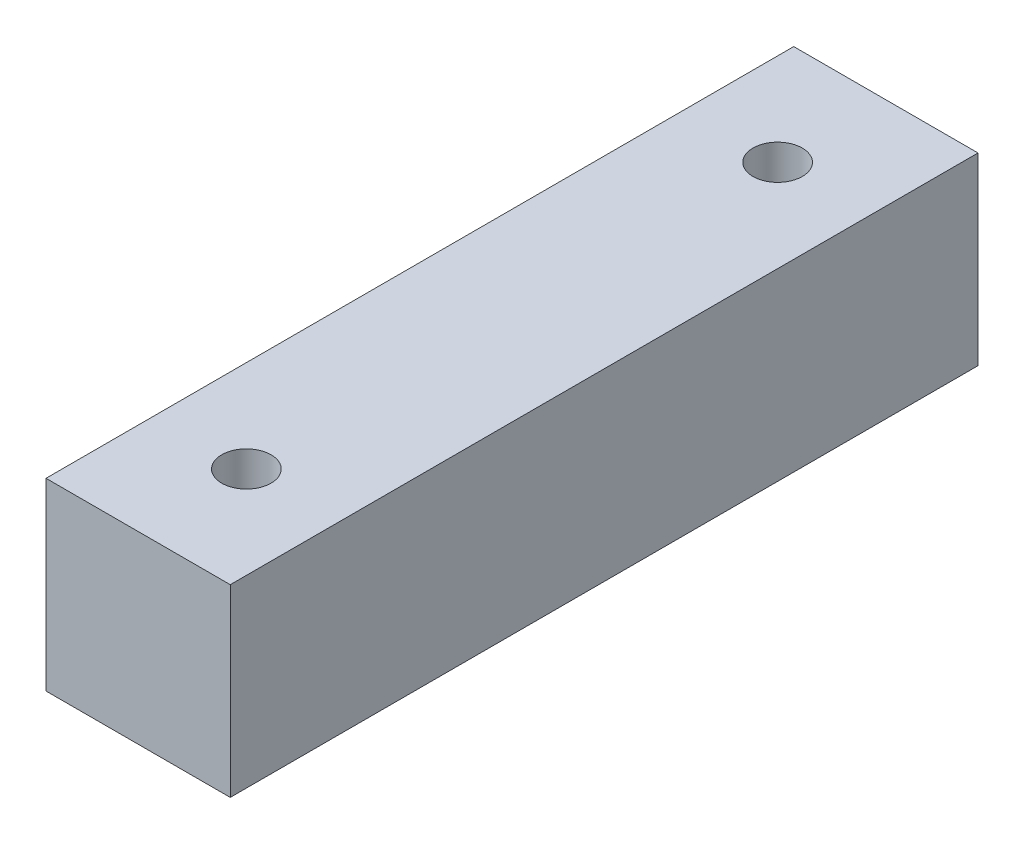
SolidWorks part; units mm, degrees
ref_plane "Front Plane" through (0, 0, 0) normal (0, 0, 1) x (1, 0, 0)
ref_plane "Top Plane" through (0, 0, 0) normal (0, 1, 0) x (1, 0, 0)
ref_plane "Right Plane" through (0, 0, 0) normal (1, 0, 0) x (0, 0, -1)
sketch "Sketch1" plane through (0, 0, 0) normal (0, 0, 1) x (1, 0, 0)
  line L1 (-6.35, -6.35) -> (6.35, -6.35)
  line L2 (-6.35, -6.35) -> (-6.35, 6.35)
  line L3 (-6.35, 6.35) -> (6.35, 6.35)
  line L4 (6.35, -6.35) -> (6.35, 6.35)
  line L5 (-6.35, -6.35) -> (6.35, 6.35) construction
  line L6 (-6.35, 6.35) -> (6.35, -6.35) construction
  point P0 (0, 0)
  dimension "D1" = 12.7
  dimension "D2" = 12.7
extrude "Boss-Extrude1" add sketch "Sketch1" along normal blind 51.5391
sketch "Sketch2" plane through (0, -6.35, 0) normal (0, -1, 0) x (1, 0, 0)
  circle A0 centre (0, 7.4612) radius 1.7
  circle A1 centre (0, 44.0779) radius 1.7
  dimension "D1" = 3.4
extrude "Cut-Extrude1" cut sketch "Sketch2" against normal through all
